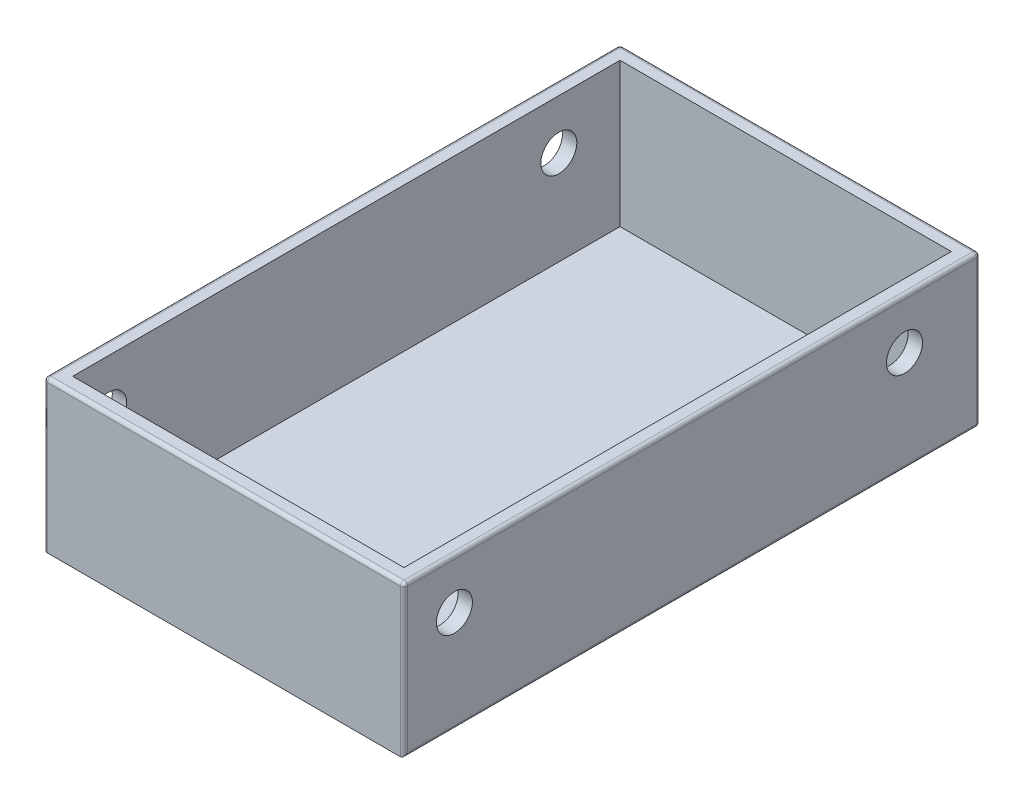
SolidWorks part; units mm, degrees
ref_plane "Front Plane" through (0, 0, 0) normal (0, 0, 1) x (1, 0, 0)
ref_plane "Top Plane" through (0, 0, 0) normal (0, 1, 0) x (1, 0, 0)
ref_plane "Right Plane" through (0, 0, 0) normal (1, 0, 0) x (0, 0, -1)
sketch "Sketch1" plane through (0, 0, 0) normal (0, 1, 0) x (1, 0, 0)
  line L1 (0, 0) -> (50, 0)
  line L2 (0, 0) -> (0, 80)
  line L3 (0, 80) -> (50, 80)
  line L4 (50, 0) -> (50, 80)
  line L5 (2, 2) -> (48, 2)
  line L6 (2, 2) -> (2, 78)
  line L7 (2, 78) -> (48, 78)
  line L8 (48, 2) -> (48, 78)
  dimension "D1" = 80
  dimension "D2" = 50
  dimension "D3" = 2
  dimension "D4" = 2
  dimension "D5" = 2
  dimension "D6" = 2
extrude "Boss-Extrude1" add sketch "Sketch1" against normal blind 5
extrude "Boss-Extrude2" add sketch "Sketch1<2>" against normal blind 5 contours L5 L8 L7 L6 region at (25, 0, -40)
sketch "Sketch1<2>" plane through (0, 0, 0) normal (0, 1, 0) x (1, 0, 0) same geometry as "Sketch1"
extrude "Boss-Extrude3" add sketch "Sketch1<3>" along normal blind 10
sketch "Sketch1<3>" plane through (0, 0, 0) normal (0, 1, 0) x (1, 0, 0) same geometry as "Sketch1"
sketch "Sketch3" plane through (50, 0, 0) normal (1, 0, 0) x (0, 0, -1)
  line L0 (0, -5) -> (0, 10) construction
  line L1 (80, -5) -> (80, 10) construction
  line L3 (2, 0) -> (78, 0) construction
  circle A0 centre (7, 8.1) radius 2.5
  circle A1 centre (69.5, 8.1) radius 2.5
  point P0 (7, 8.1)
  point P1 (69.5, 8.1)
  dimension "D5" = 5
  dimension "D6" = 5
  dimension "D1" = 7
  dimension "D2" = 10.5
  dimension "D3" = 8.1
  dimension "D4" = 8.1
extrude "Cut-Extrude2" cut sketch "Sketch1<4>" against normal blind 49 contours L5 L8 L7 L6 region at (25, 0, -40)
sketch "Sketch1<4>" plane through (0, 0, 0) normal (0, 1, 0) x (1, 0, 0) same geometry as "Sketch1"
extrude "Cut-Extrude3" cut sketch "Sketch3" against normal blind 49
extrude "Boss-Extrude4" add sketch "Sketch1<5>" against normal blind 1 from offset 5 separate body contours L5 L8 L7 L6 region at (25, 0, -40) offset against normal yes
sketch "Sketch1<5>" plane through (0, 0, 0) normal (0, 1, 0) x (1, 0, 0) same geometry as "Sketch1"
extrude "Boss-Extrude5" add sketch "Sketch1<6>" against normal blind 1 from offset 5 contours L1 L4 L3 L2 L8 L5 L6 L7 region at (0.9434, 0, -40) offset against normal yes
sketch "Sketch1<6>" plane through (0, 0, 0) normal (0, 1, 0) x (1, 0, 0) same geometry as "Sketch1"
extrude "Boss-Extrude6" add sketch "Sketch1<7>" along normal blind 15
sketch "Sketch1<7>" plane through (0, 0, 0) normal (0, 1, 0) x (1, 0, 0) same geometry as "Sketch1"
extrude "Cut-Extrude4" cut sketch "Sketch3<2>" against normal blind 61
sketch "Sketch3<2>" plane through (50, 0, 0) normal (1, 0, 0) x (0, 0, -1) same geometry as "Sketch3"
sketch "Sketch4" plane through (0, 0, 0) normal (-1, 0, 0) x (0, 0, 1)
  circle A0 centre (-69.5, 8.1) radius 2.5
  circle A1 centre (-7, 8.1) radius 2.5
fillet "Fillet1" radius 0.5 12 edges at (50, 4.5, 0) (0, 4.5, 0) (0, 4.5, -80) (50, 4.5, -80) (25, -5, -2) (0, -6, -40) (50, -6, -40) (25, -6, -80) (25, 15, 0) (50, 15, -40) (0, 15, -40) (25, 15, -80)
